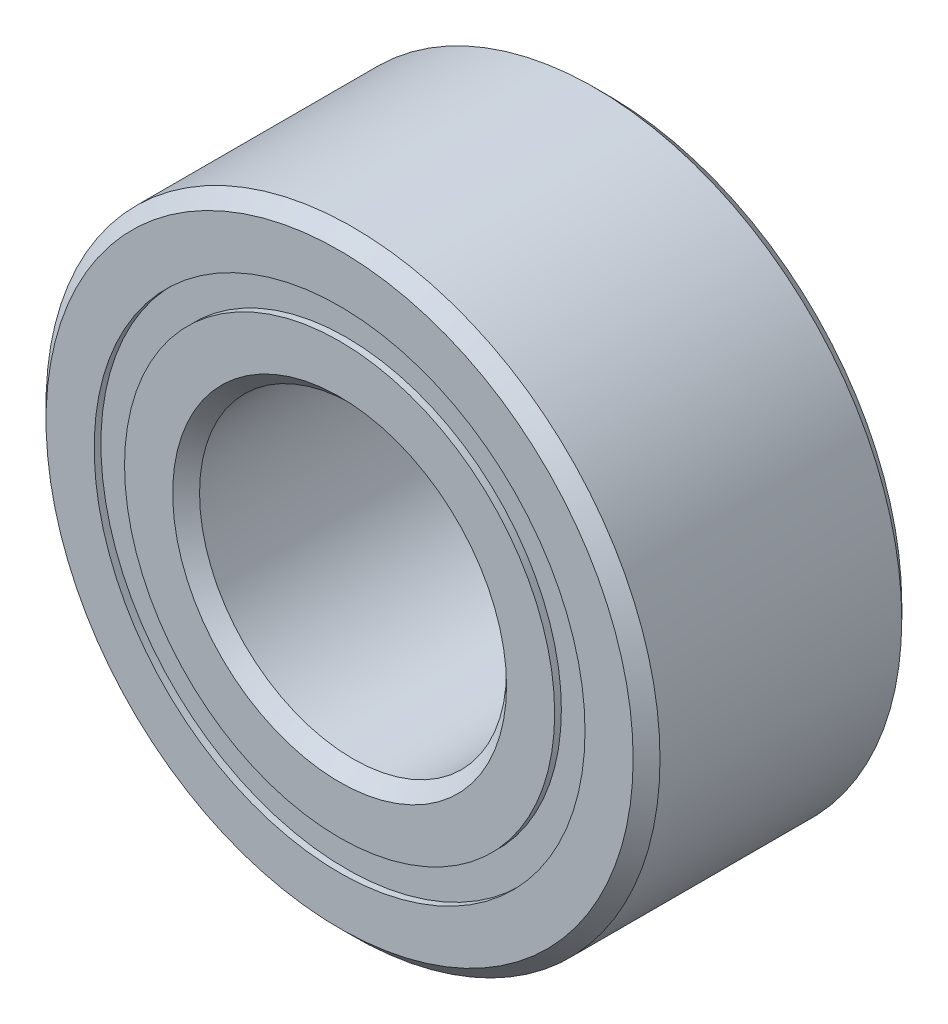
SolidWorks part; units mm, degrees
ref_plane "Front Plane" through (0, 0, 0) normal (0, 0, 1) x (1, 0, 0)
ref_plane "Top Plane" through (0, 0, 0) normal (0, 1, 0) x (1, 0, 0)
ref_plane "Right Plane" through (0, 0, 0) normal (1, 0, 0) x (0, 0, -1)
sketch "Sketch1" plane through (0, 0, 0) normal (1, 0, 0) x (0, 0, -1)
  line L0 (-1.3891, 0) -> (1.3891, 0) construction
  line L1 (0, 3.175) -> (0, -3.175) construction
  line L2 (1.2502, 3.175) -> (-1.2502, 3.175)
  line L3 (-1.2502, 3.175) -> (-1.3891, 3.0361)
  line L4 (-1.3891, 3.0361) -> (-1.3891, 2.5383)
  line L5 (-1.3891, 2.5383) -> (-0.6174, 2.5383)
  line L6 (1.3891, 2.5383) -> (0.6174, 2.5383)
  line L7 (1.3891, 3.0361) -> (1.3891, 2.5383)
  line L8 (1.2502, 3.175) -> (1.3891, 3.0361)
  line L9 (0, 3.175) -> (0, 2.3812) construction
  line L10 (0, 2.3812) -> (0, 1.5875) construction
  arc A0 (-0.6174, 2.5383) -> (0.6174, 2.5383) centre (0, 2.3812) cw
  point P14 (0, 1.5875)
  dimension "Width" = 2.7781
  dimension "OD" = 6.35
  dimension "D1" = 45
  dimension "D2" = 0.1389
  dimension "D3" = 1.2347
  dimension "D4" = 0.157
revolve "Revolve1" add sketch "Sketch1" angle 360 about L0
sketch "Sketch3" plane through (0, 0, 0) normal (1, 0, 0) x (0, 0, -1)
  line L0 (-0.6174, 2.2242) -> (-1.3891, 2.2242)
  line L1 (-1.3891, 3.0361) -> (-1.3891, 2.5383) construction
  line L2 (-1.2502, 3.175) -> (-1.3891, 3.0361) construction
  line L3 (-1.3891, 2.2242) -> (-1.3891, 1.7264)
  line L5 (-1.3891, 1.7264) -> (-1.2502, 1.5875)
  line L6 (-1.2502, 1.5875) -> (1.2502, 1.5875)
  line L7 (1.2502, 3.175) -> (1.2502, -3.175) construction
  line L8 (1.2502, 1.5875) -> (1.3891, 1.7264)
  line L9 (1.3891, -3.0361) -> (1.3891, 3.0361) construction
  line L10 (1.3891, 1.7264) -> (1.3891, 2.2242)
  line L11 (1.3891, 2.2242) -> (0.6174, 2.2242)
  line L12 (0, 3.175) -> (0, -3.175) construction
  line L13 (1.2502, 3.175) -> (1.3891, 3.0361) construction
  arc A1 (0.6174, 2.2242) -> (-0.6174, 2.2242) centre (0, 2.3812) cw
  arc A2 (0.6174, 2.5383) -> (-0.6174, 2.5383) centre (0, 2.3812) ccw construction
revolve "Revolve3" add sketch "Sketch3" angle 360 about L0
sketch "Sketch4" plane through (0, 0, 0) normal (1, 0, 0) x (0, 0, -1)
  line L0 (-0.637, 2.3812) -> (0.637, 2.3812)
  arc A2 (-0.637, 2.3812) -> (0.637, 2.3812) centre (0, 2.3812) cw
  arc A3 (0.6174, 2.5383) -> (-0.6174, 2.5383) centre (0, 2.3812) ccw construction
revolve "Revolve4" add sketch "Sketch4" angle 360 about L0
ref_axis "Axis1" through (0, 0, -1.3891) along (0, 0, 1)
pattern_circular "CirPattern1" count 10 every 36 about axis through (0, 0, -1.3891) along (0, 0, 1) of bodies 104
sketch "Sketch5" plane through (0, 0, 0) normal (1, 0, 0) x (0, 0, -1)
  line L0 (-1.3891, 2.5383) -> (-0.6174, 2.5383) construction
  line L1 (-1.3196, 2.5383) -> (-0.637, 2.5383)
  line L2 (-1.3196, 2.5383) -> (-1.3196, 2.2242)
  line L3 (-1.3196, 2.2242) -> (-0.637, 2.2242)
  line L4 (-0.637, 2.5383) -> (-0.637, 2.2242)
  line L5 (-0.6174, 2.2242) -> (-1.3891, 2.2242) construction
  line L6 (1.3891, 2.5383) -> (0.6174, 2.5383) construction
  line L7 (1.3196, 2.5383) -> (0.637, 2.5383)
  line L8 (1.3196, 2.5383) -> (1.3196, 2.2242)
  line L9 (1.3196, 2.2242) -> (0.637, 2.2242)
  line L10 (0.637, 2.5383) -> (0.637, 2.2242)
  line L11 (1.3891, 2.2242) -> (0.6174, 2.2242) construction
  line L12 (-1.2502, 3.175) -> (-1.3891, 3.0361) construction
  point P18 (-1.3196, 3.1055)
revolve "Revolve5" add sketch "Sketch5" angle 360 about L0
equation "\"D2@Sketch1\" = \"Width@Sketch1\"*.05"
equation "\"D3@Sketch1\" = \"Width@Sketch1\"/2.25"
equation "\"D4@Sketch1\" = (((\"OD@Sketch1\"-\"Width@Sketch1\")/2)/3.25)/3.5"
equation "\"D2@CirPattern1\" = 360/\"Balls@CirPattern1\""
